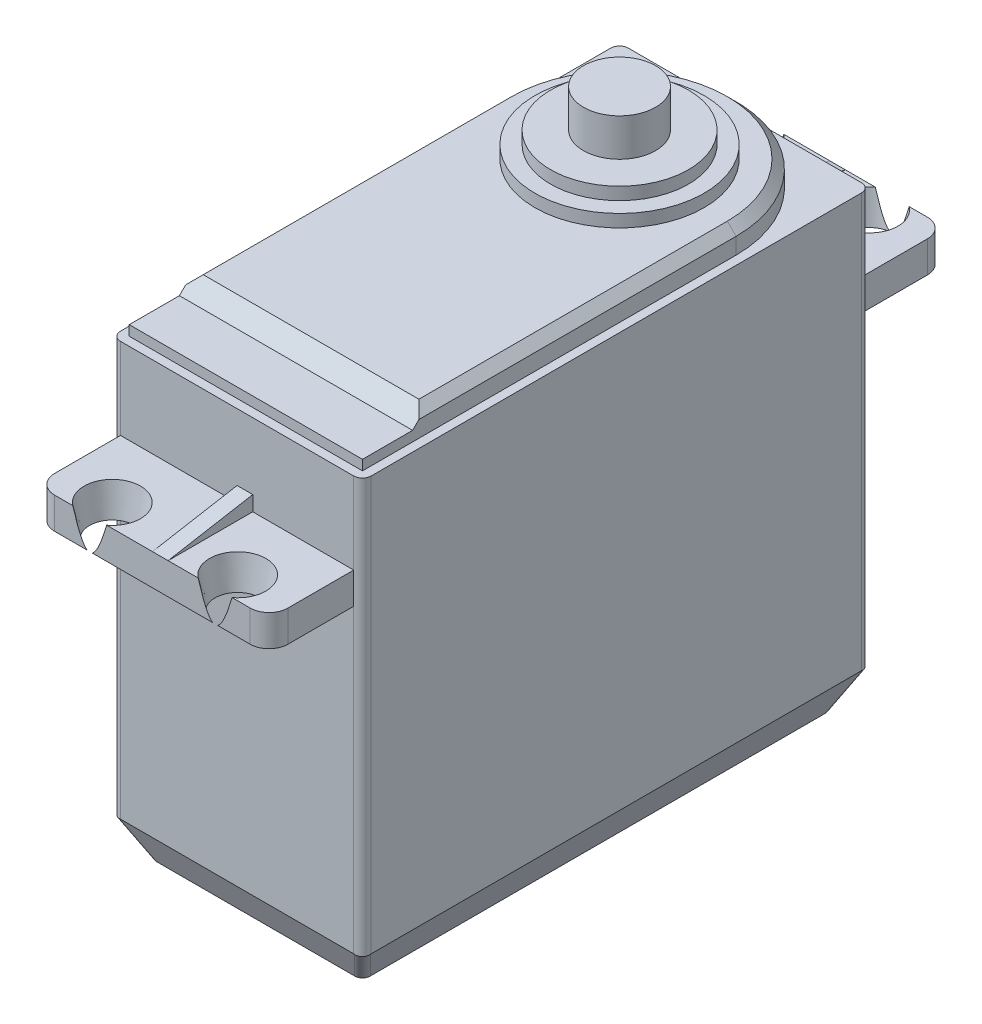
SolidWorks part; units mm, degrees
ref_plane "Front Plane" through (0, 0, 0) normal (0, 0, 1) x (1, 0, 0)
ref_plane "Top Plane" through (0, 0, 0) normal (0, 1, 0) x (1, 0, 0)
ref_plane "Right Plane" through (0, 0, 0) normal (1, 0, 0) x (0, 0, -1)
sketch "Sketch1" plane through (0, 0, 0) normal (0, 1, 0) x (1, 0, 0)
  line L1 (-10, -20.25) -> (10, -20.25)
  line L2 (-10, -20.25) -> (-10, 20.25)
  line L3 (-10, 20.25) -> (10, 20.25)
  line L4 (10, -20.25) -> (10, 20.25)
  line L5 (-10, -20.25) -> (10, 20.25) construction
  line L6 (-10, 20.25) -> (10, -20.25) construction
  point P0 (0, 0)
  dimension "D1" = 40.5
  dimension "D2" = 20
extrude "Boss-Extrude1" add sketch "Sketch1" along normal mid plane 36
sketch "Sketch2" plane through (0, 18, 0) normal (0, 1, 0) x (1, 0, 0)
  line L0 (10, 20.25) -> (-10, 20.25) construction
  line L1 (10, -20.25) -> (10, 20.25) construction
  line L2 (-10, 10.25) -> (-10, -20.25) construction
  line L3 (-10, -20.25) -> (10, -20.25) construction
  line L4 (10, -20.25) -> (10, 10.25) construction
  line L5 (-9.3, 10.25) -> (-9.3, -19.55)
  line L6 (-9.3, -19.55) -> (9.3, -19.55)
  line L7 (9.3, -19.55) -> (9.3, 10.25)
  arc A0 (10, 10.25) -> (-10, 10.25) centre (0, 10.25) ccw construction
  arc A1 (9.3, 10.25) -> (-9.3, 10.25) centre (0, 10.25) ccw
  dimension "D1" = 0.7
extrude "Boss-Extrude2" add sketch "Sketch2" along normal blind 2
sketch "Sketch4" plane through (0, 0, 0) normal (1, 0, 0) x (0, 0, -1)
  line L0 (10.25, 20) -> (10.25, 25)
  line L1 (10.25, 25) -> (13.125, 25)
  line L2 (13.125, 25) -> (13.125, 22)
  line L3 (13.125, 22) -> (15.75, 22)
  line L4 (15.75, 22) -> (15.75, 21)
  line L5 (15.75, 21) -> (17, 21)
  line L6 (17, 21) -> (17, 20)
  line L7 (19.55, 20) -> (10.25, 20) construction
  line L8 (17, 20) -> (10.25, 20)
  line L9 (-20.25, -18) -> (20.25, -18) construction
  dimension "D1" = 43
  dimension "D2" = 1
  dimension "D3" = 6.75
  dimension "D4" = 5.5
  dimension "D5" = 2.875
revolve "Revolve1" add sketch "Sketch4" angle 360 about L0
ref_plane "Plane1" through (0, 9, 0) normal (0, -1, 0) x (-1, 0, 0)
sketch "Sketch5" plane through (0, 9, 0) normal (0, -1, 0) x (-1, 0, 0)
  line L0 (-10, 20.25) -> (10, 20.25) construction
  line L1 (9.3, 20.25) -> (-9.3, 20.25)
  line L2 (9.3, 20.25) -> (9.3, 27)
  line L3 (9.3, 27) -> (-9.3, 27)
  line L4 (-9.3, 20.25) -> (-9.3, 27)
  line L5 (0, 0) -> (-10, 0) construction
  line L6 (-10, -20.25) -> (-10, 20.25) construction
  line L7 (-9.3, -20.25) -> (-9.3, -27)
  line L8 (9.3, -27) -> (-9.3, -27)
  line L9 (9.3, -20.25) -> (9.3, -27)
  line L10 (9.3, -20.25) -> (-9.3, -20.25)
  line L11 (0, 0) -> (0, -20.25) construction
  circle A0 centre (-5, 25.2) radius 1.8 construction
  circle A1 centre (-5, -25.2) radius 1.8 construction
  circle A2 centre (5, 25.2) radius 1.8 construction
  circle A3 centre (5, -25.2) radius 1.8 construction
  circle A4 centre (5, 25.2) radius 2.25
  circle A5 centre (-5, 25.2) radius 2.25
  circle A6 centre (5, -25.2) radius 2.25
  circle A7 centre (-5, -25.2) radius 2.25
  point P6 (0, 20.25)
  point P12 (0, -20.25)
  point P21 (-5, 23.4)
  point P22 (-5, -23.4)
  dimension "D4" = 3.6
  dimension "D6" = 4.5
  dimension "D1" = 0.7
  dimension "D2" = 54
  dimension "D3" = 46.8
  dimension "D5" = 10
  dimension "D7" = 50.4
extrude "Boss-Extrude3" add sketch "Sketch5" against normal blind 2.5 contours A5 L3 L4 L1 L2 A4 | A7 L8 A6 L9 L10 L7 region at (0, 9, -23.1616) region at (0, 9, 23.1616)
fillet "Fillet1" radius 1.5 4 edges at (9.3, 10.25, -27) (-9.3, 10.25, -27) (9.3, 10.25, 27) (-9.3, 10.25, 27)
sketch "Sketch6" plane through (0, 0, 0) normal (1, 0, 0) x (0, 0, -1)
  line L0 (20.25, 11.5) -> (27, 11.5)
  line L1 (27, 11.5) -> (20.25, 12.6902)
  line L2 (20.25, 18) -> (20.25, -18) construction
  line L3 (20.25, 12.6902) -> (20.25, 11.5)
  line L4 (0, 0) -> (0, -18) construction
  line L5 (-20.25, -18) -> (20.25, -18) construction
  line L6 (-20.25, 12.6902) -> (-20.25, 11.5)
  line L7 (-27, 11.5) -> (-20.25, 12.6902)
  line L8 (-20.25, 11.5) -> (-27, 11.5)
  dimension "D1" = 10
extrude "Boss-Extrude4" add sketch "Sketch6" along normal blind 1.25
draft "Draft1" type of draft neutral plane draft angle 10 faces to draft 4 face at (5, 10.25, 24.975) face at (-5, 10.25, 24.975) face at (-5, 10.25, -24.975) face at (5, 10.25, -24.975) neutral plane through (0, 11.5, 0) neutral plane normal (0, 1, 0) parameters "D1"=10
sketch "Sketch7" plane through (0, 0, -20.25) normal (0, 0, -1) x (-1, 0, 0)
  line L0 (-10, -18) -> (10, -18) construction
  line L1 (-3.5, -14.5) -> (3.5, -14.5)
  line L2 (-3.5, -14.5) -> (-3.5, -10.5)
  line L3 (-3.5, -10.5) -> (3.5, -10.5)
  line L4 (3.5, -14.5) -> (3.5, -10.5)
  line L5 (-3.5, -14.5) -> (3.5, -10.5) construction
  line L6 (-3.5, -10.5) -> (3.5, -14.5) construction
  point P0 (0, -12.5)
  dimension "D1" = 5.5
  dimension "D2" = 4
  dimension "7" = 7
extrude "Boss-Extrude5" add sketch "Sketch7" along normal blind 5
sketch "Sketch8" plane through (0, 0, 0) normal (1, 0, 0) x (0, 0, -1)
  line L0 (-19.55, 18.8) -> (-15.55, 18.8)
  line L1 (-19.55, 20) -> (-19.55, 18) construction
  line L2 (-15.55, 18.8) -> (-14.35, 20)
  line L3 (-19.55, 20) -> (10.25, 20) construction
  line L4 (-14.35, 20) -> (-19.55, 20)
  line L5 (-19.55, 20) -> (-19.55, 18.8)
  line L6 (-20.25, 18) -> (20.25, 18) construction
  dimension "D1" = 0.8
  dimension "D2" = 4
  dimension "D3" = 45
extrude "Cut-Extrude1" cut sketch "Sketch8" against normal through all both and the other way through all
chamfer "Chamfer1" distance 0.7 angle 45 3 edges at (-9.3, 20, 2.05) (0, 20, -19.55) (9.3, 20, 2.05)
chamfer "Chamfer2" distance 1.5 distance2 3 4 edges at (0, -18, -20.25) (-10, -18, 0) (0, -18, 20.25) (10, -18, 0) first distance on face at (0, -18, 0)
fillet "Fillet2" radius 0.7 8 edges at (-9.25, -16.5, -19.5) (-9.25, -16.5, 19.5) (9.25, -16.5, -19.5) (9.25, -16.5, 19.5) (10, 1.5, -20.25) (10, 1.5, 20.25) (-10, 1.5, 20.25) (-10, 1.5, -20.25)
